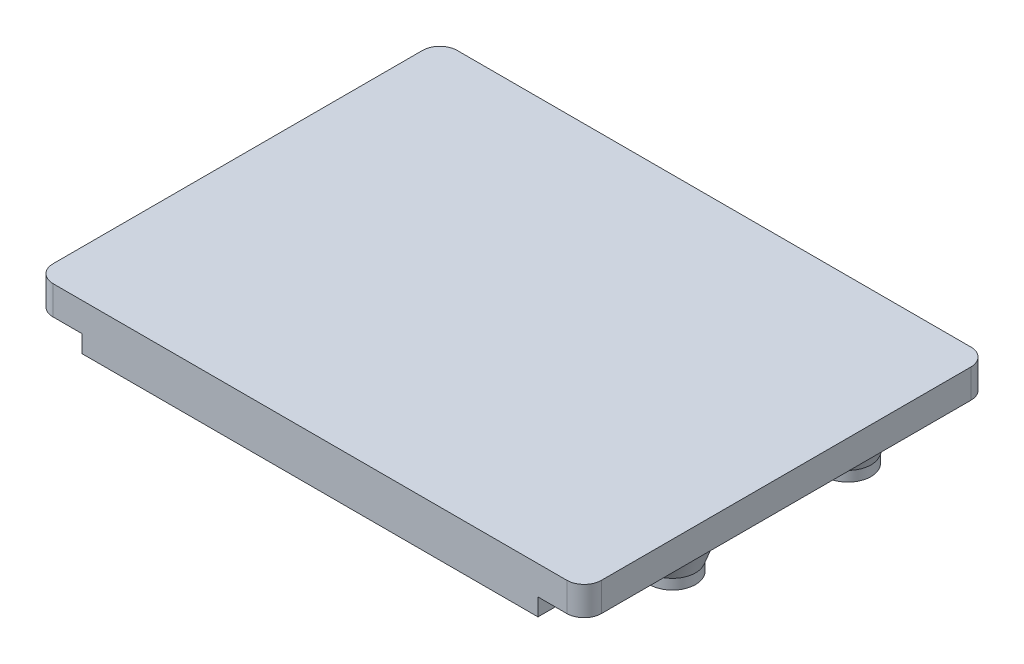
SolidWorks part; units mm, degrees
ref_plane "Plan de face" through (0, 0, 0) normal (0, 0, 1) x (1, 0, 0)
ref_plane "Plan de dessus" through (0, 0, 0) normal (0, 1, 0) x (1, 0, 0)
ref_plane "Plan de droite" through (0, 0, 0) normal (1, 0, 0) x (0, 0, -1)
sketch "Esquisse1" plane through (0, 0, 0) normal (0, 1, 0) x (1, 0, 0)
  line L1 (-47.5, 35) -> (47.5, 35)
  line L2 (-47.5, 35) -> (-47.5, -35)
  line L3 (-47.5, -35) -> (47.5, -35)
  line L4 (47.5, 35) -> (47.5, -35)
  dimension "D1" = 95
  dimension "D2" = 70
  dimension "D3" = 47.5
  dimension "D4" = 35
extrude "Extrusion1" add sketch "Esquisse1" along normal blind 5
sketch "Esquisse2" plane through (0, 0, 0) normal (0, -1, 0) x (1, 0, 0)
  line L0 (-47.5, 35) -> (47.5, 35) construction
  line L2 (-39.5, 35) -> (39.5, 35)
  line L3 (-39.5, 35) -> (-39.5, 30)
  line L4 (-39.5, 30) -> (39.5, 30)
  line L6 (39.5, 35) -> (39.5, 30)
  line L7 (47.5, -35) -> (-47.5, -35) construction
  line L8 (-28.5, -30) -> (29.5, -30)
  line L9 (-28.5, -30) -> (-28.5, -35)
  line L10 (-28.5, -35) -> (29.5, -35)
  line L11 (29.5, -30) -> (29.5, -35)
  line L12 (-47.5, -35) -> (-47.5, 35) construction
  line L13 (-47.5, -5.5) -> (-42.5, -5.5)
  line L14 (-47.5, -5.5) -> (-47.5, -14.5)
  line L16 (-47.5, -14.5) -> (-42.5, -14.5)
  line L17 (-42.5, -5.5) -> (-42.5, -14.5)
  dimension "D1" = 8
  dimension "D2" = 79
  dimension "D3" = 20.5
  dimension "D4" = 9
  dimension "D5" = 19
  dimension "D6" = 58
  dimension "D7" = 5
  dimension "D8" = 5
  dimension "D9" = 5
extrude "Extrusion2" add sketch "Esquisse2" along normal blind 3
sketch "Esquisse3" plane through (0, 0, 0) normal (0, -1, 0) x (1, 0, 0)
  line L0 (-47.5, -35) -> (-47.5, -14.5) construction
  line L1 (-47.5, 9.5) -> (-42.5, 9.5)
  line L2 (-47.5, 9.5) -> (-47.5, 0.5)
  line L3 (-47.5, 0.5) -> (-42.5, 0.5)
  line L4 (-42.5, 9.5) -> (-42.5, 0.5)
  line L7 (-42.5, -5.5) -> (-47.5, -5.5) construction
  dimension "D1" = 5
  dimension "D2" = 6
  dimension "D3" = 9
extrude "Extrusion3" add sketch "Esquisse3" along normal blind 5
fillet "Congé1" radius 3 4 edges at (47.5, 2.5, -35) (-47.5, 2.5, -35) (-47.5, 2.5, 35) (47.5, 2.5, 35)
sketch "Esquisse5" plane through (0, 0, 0) normal (0, -1, 0) x (1, 0, 0)
  line L0 (47.5, 32) -> (47.5, -32) construction
  line L1 (39.5, 35) -> (-39.5, 35) construction
  line L2 (44.5, -35) -> (29.5, -35) construction
  line L3 (-47.5, -32) -> (-47.5, -14.5) construction
  line L4 (-47.5, 9.5) -> (-47.5, 32) construction
  line L5 (-28.5, -35) -> (-44.5, -35) construction
  circle A0 centre (-25.5, 10.5) radius 1.6
  circle A1 centre (37.3, 9.5) radius 1.6
  circle A2 centre (36.3, -21.9) radius 1.6
  circle A3 centre (-36.5, -23.5) radius 1.6
  circle A4 centre (-25.5, 10.5) radius 4
  circle A5 centre (37.3, 9.5) radius 4
  circle A6 centre (36.3, -21.9) radius 4
  circle A7 centre (-36.5, -23.5) radius 4
  point P15 (-47.5, -23.25)
  dimension "D9" = 3.2
  dimension "D10" = 3.2
  dimension "D11" = 3.2
  dimension "D12" = 3.2
  dimension "D13" = 8
  dimension "D14" = 8
  dimension "D15" = 8
  dimension "D16" = 8
  dimension "D1" = 10.2
  dimension "D2" = 25.5
  dimension "D3" = 13.1
  dimension "D4" = 11.2
  dimension "D5" = 11
  dimension "D6" = 22
  dimension "D7" = 11.5
  dimension "D8" = 24.5
extrude "Extrusion4" add sketch "Esquisse5" along normal blind 10
chamfer "Chanfrein1" distance 3 angle 70 4 edges at (-25.5, 0, 14.5) (-36.5, 0, -19.5) (36.3, 0, -17.9) (37.3, 0, 13.5) first distance on face at (-15.125, 0, -0.8333)
